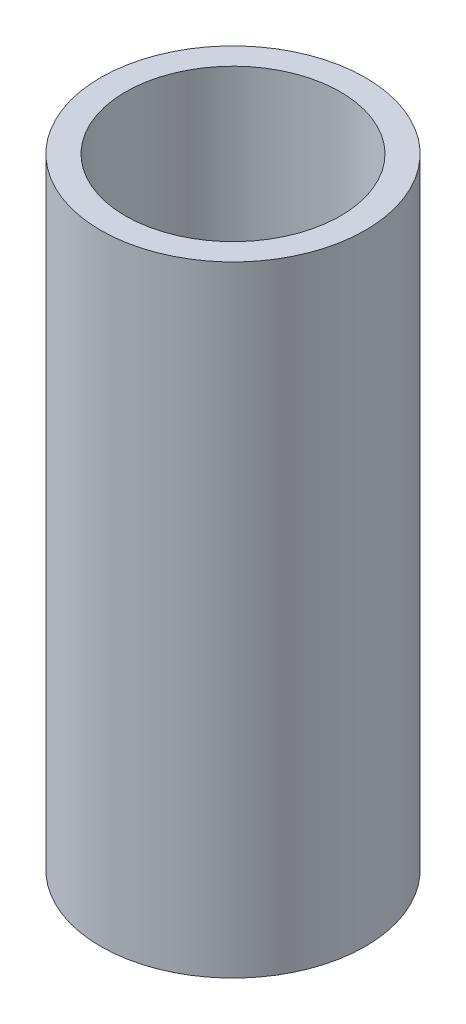
SolidWorks part; units mm, degrees
ref_plane "Front Plane" through (0, 0, 0) normal (0, 0, 1) x (1, 0, 0)
ref_plane "Top Plane" through (0, 0, 0) normal (0, 1, 0) x (1, 0, 0)
ref_plane "Right Plane" through (0, 0, 0) normal (1, 0, 0) x (0, 0, -1)
sketch "Sketch1" plane through (0, 0, 0) normal (0, 1, 0) x (1, 0, 0)
  circle A0 centre (0, 0) radius 17.5
  dimension "SLEEVE_OD" = 35
extrude "Boss-Extrude1" add sketch "Sketch1" along normal blind 82.0235
sketch "Sketch2" plane through (0, 0, 0) normal (0, 1, 0) x (1, 0, 0)
  circle A0 centre (0, 0) radius 14.2152
  dimension "BORE_D" = 28.4304
extrude "Cut-Extrude1" cut sketch "Sketch2" along normal through all
chamfer "Chamfer1" distance 2.6732 angle 45 rebuild error yes
